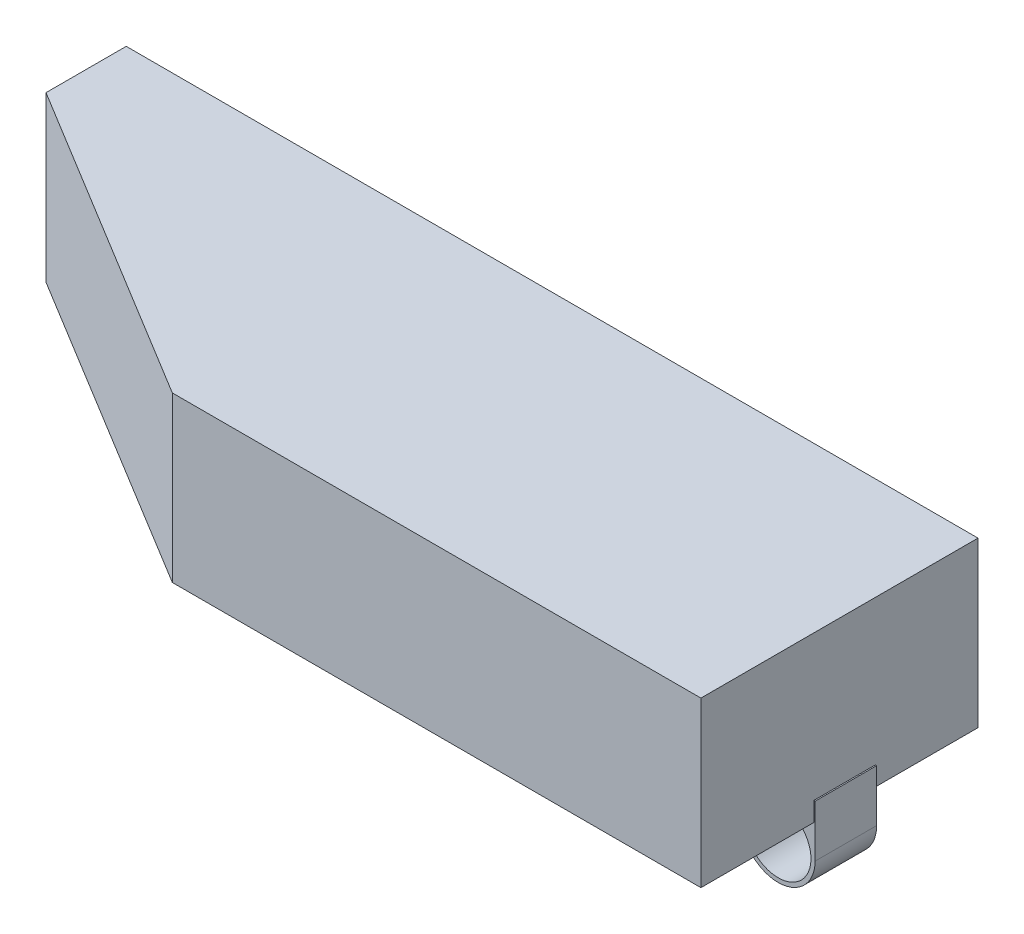
SolidWorks part; units mm, degrees
ref_plane "Ön Düzlem" through (0, 0, 0) normal (0, 0, 1) x (1, 0, 0)
ref_plane "Üst Düzlem" through (0, 0, 0) normal (0, 1, 0) x (1, 0, 0)
ref_plane "Sağ Düzlem" through (0, 0, 0) normal (1, 0, 0) x (0, 0, -1)
sketch "Çizim3" plane through (0, 0, 0) normal (0, 1, 0) x (1, 0, 0)
  line L0 (-257.5343, 0.0002) -> (-415, 95.9159)
  line L1 (-415, 95.9159) -> (-415, 135)
  line L2 (-415, 135) -> (0, 135)
  line L3 (0, 135) -> (0, 0)
  line L4 (-257.5343, 0.0002) -> (0, 0)
  point P0 (0, 0)
  point P1 (-17.3808, 0)
  point P2 (-415, 95.9159)
  point P5 (-257.5343, 0.0002)
  point P10 (-217.3808, 0.0002)
  dimension "D1" = 184.378
  dimension "D2" = 184.378
  dimension "D3" = 148.654
  dimension "D4" = 135
  dimension "D5" = 415
  dimension "D6" = 40.1536
  dimension "D7" = 200
  dimension "D8" = 17.3808
extrude "Yükseklik-Ekstrüzyon1" add sketch "Çizim3" along normal blind 80 contours L0 L1 L2 L3 L4
sketch "Çizim4" plane through (0, 0, -135) normal (0, 0, -1) x (-1, 0, 0)
  line L0 (-0.6192, -16) -> (-0.6192, 9.3077)
  line L1 (415, 0) -> (0, 0) construction
  line L2 (217.3808, 0) -> (217.3808, -188.474) construction
  line L3 (-0.6192, 9.3077) -> (35.3808, 9.3077)
  line L4 (35.3808, 9.3077) -> (35.3808, -16)
  line L5 (199.3808, -16) -> (199.3808, 11.2539)
  line L6 (199.3808, 11.2539) -> (235.3808, 11.2539)
  line L7 (235.3808, 11.2539) -> (235.3808, -16)
  circle A0 centre (17.3808, -16) radius 16
  arc A1 (-0.6192, -16) -> (35.3808, -16) centre (17.3808, -16) ccw
  circle A2 centre (217.3808, -16) radius 16
  circle A3 centre (217.3808, -16) radius 18
  line M3 (0, 0) -> (415, 0)
  line M6 (0, 80) -> (0, 0)
  dimension "D1" = 32
  dimension "D2" = 36
  dimension "D3" = 32
  dimension "D4" = 36
extrude "Yükseklik-Ekstrüzyon6" add sketch "Çizim4" against normal blind 30 from offset 50 contours L4 L3 M6 M3 | L0 A1 L4 A0 L3 M3 M6 | A3 L7 L6 L5 M3 | A3 L5 M3 | A3 L7 M3 | L2 A2 A3 M3 | A2 L2 A3 M3 | A3 M3 region at (-217.3808, 5.9072, -135) region at (-202.0929, -3.7522, -135) region at (0.0561, -3.3462, -135) region at (-17.6904, 4.6538, -135) region at (-202.3399, -6.8309, -135) region at (-217.3808, 0.8039, -135) region at (-217.7655, -33, -135) region at (-232.6686, -3.7522, -135) offset against normal yes
